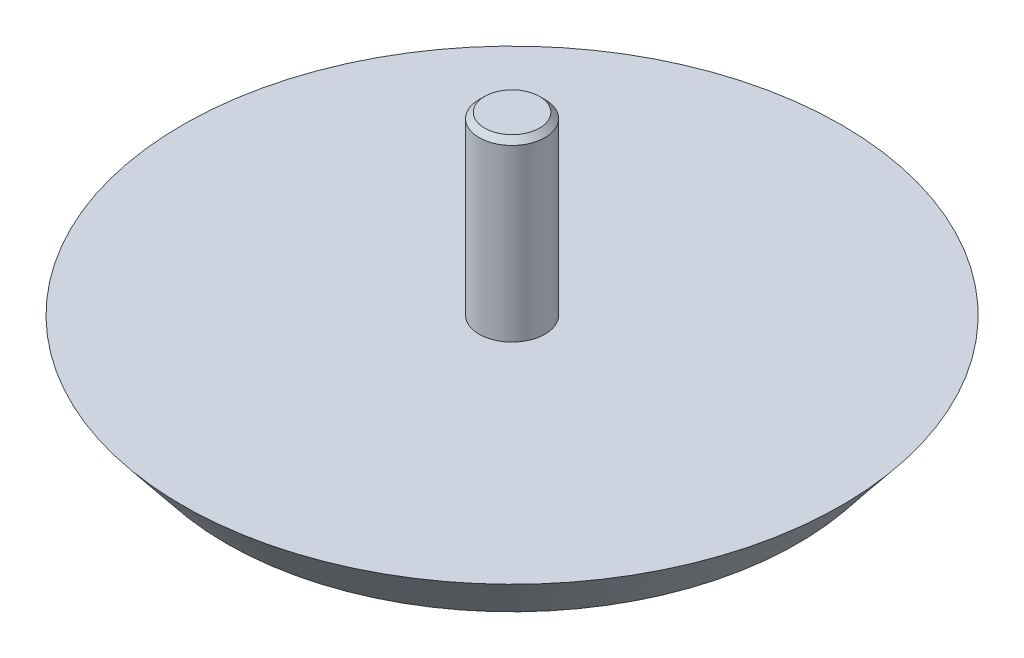
SolidWorks part; units mm, degrees
ref_plane "Plan de face" through (0, 0, 0) normal (0, 0, 1) x (1, 0, 0)
ref_plane "Plan de dessus" through (0, 0, 0) normal (0, 1, 0) x (1, 0, 0)
ref_plane "Plan de droite" through (0, 0, 0) normal (1, 0, 0) x (0, 0, -1)
sketch "Esquisse1" plane through (0, 0, 0) normal (0, 1, 0) x (1, 0, 0)
  circle A0 centre (0, 0) radius 3
  dimension "D1" = 6
extrude "Boss.-Extru.1" add sketch "Esquisse1" along normal blind 16
sketch "Esquisse4" plane through (0, 0, 0) normal (1, 0, 0) x (0, 0, -1)
  line L0 (0, 0) -> (30, 0)
  line L1 (30, 0) -> (26, -5)
  line L2 (26, -5) -> (0, -5)
  line L3 (0, -5) -> (0, 0)
  dimension "D1" = 5
  dimension "D2" = 30
  dimension "D3" = 26
revolve "Révolution1" add sketch "Esquisse4" angle 360 about L3
chamfer "Chanfrein1" distance 0.5 angle 45 1 edges at (0, 16, 3)
